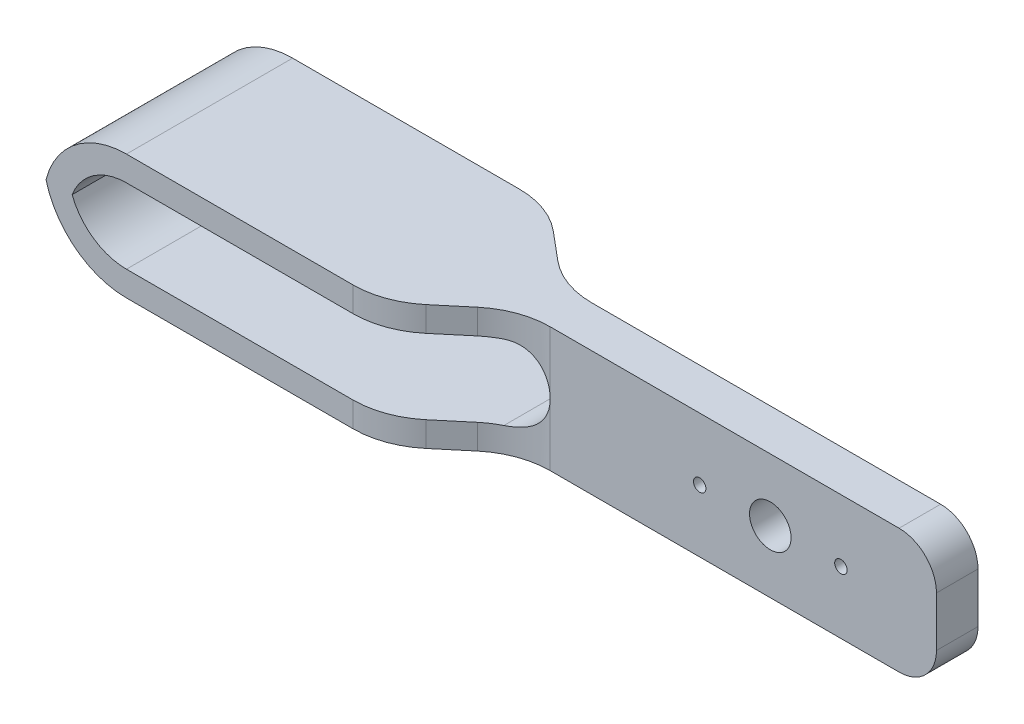
SolidWorks part; units mm, degrees
ref_plane "Plano frontal" through (0, 0, 0) normal (0, 0, 1) x (1, 0, 0)
ref_plane "Plano superior" through (0, 0, 0) normal (0, 1, 0) x (1, 0, 0)
ref_plane "Plano direito" through (0, 0, 0) normal (1, 0, 0) x (0, 0, -1)
sketch "Esboço1" plane through (0, 0, 0) normal (0, 0, 1) x (1, 0, 0)
  line L13 (-17.5, -6) -> (22.5, -6)
  line L14 (-17.5, -6) -> (-17.5, 9)
  line L15 (-17.5, 9) -> (22.5, 9)
  line L16 (22.5, -6) -> (22.5, 9)
  dimension "D3" = 15
  dimension "D4" = 40
extrude "Ressalto-extrusão1" add sketch "Esboço1" against normal blind 3 contours L13 L16 L15 L14 region at (2.5, 1.5, 0)
sketch "Esboço2" plane through (0, 0, 0) normal (0, 0, 1) x (1, 0, 0)
  line L0 (-17.5, 9) -> (22.5, -6) construction
  line L7 (-17.5, -6) -> (22.5, 9) construction
  circle A0 centre (2.5, 1.5) radius 2.5
  circle A4 centre (-6, 1.5) radius 0.75
  point P11 (0, 0)
  dimension "D1" = 1.5
  dimension "D3" = 5
  dimension "D2" = 8.5
sketch "Esboço3" plane through (0, 0, 0) normal (0, 0, 1) x (1, 0, 0)
  line L1 (-17.5, -6) -> (22.5, -6)
  line L2 (-17.5, -6) -> (-17.5, 9)
  line L3 (-17.5, 9) -> (22.5, 9)
  line L4 (22.5, -6) -> (22.5, 9)
extrude "Ressalto-extrusão2" add sketch "Esboço3" along normal blind 2
extrude "Corte-extrusão1" cut sketch "Esboço2" along normal up to surface and the other way up to surface up to face at (2.5, 1.5, 2) other way up to face at (2.5, 1.5, -3)
sketch "Esboço4" plane through (0, 9, 0) normal (0, 1, 0) x (1, 0, 0)
  line L0 (22.5, -2) -> (-17.5, -2) construction
  line L1 (6.2, -34.5) -> (-6.2, -34.5)
  line L2 (6.2, -34.5) -> (6.2, -11.5)
  line L3 (6.2, -11.5) -> (-6.2, -11.5)
  line L4 (-6.2, -34.5) -> (-6.2, -11.5)
  line L5 (-17.5, 3) -> (22.5, 3) construction
  line L6 (17.5, -2) -> (-12.5, -2)
  line L7 (17.5, -2) -> (17.5, -42)
  line L8 (17.5, -42) -> (-12.5, -42)
  line L9 (-12.5, -2) -> (-12.5, -42)
  line L10 (-12.5, -2) -> (17.5, -2)
  line L11 (-12.5, -2) -> (-12.5, 3)
  line L12 (-12.5, 3) -> (17.5, 3)
  line L13 (17.5, -2) -> (17.5, 3)
  circle A0 centre (0, -9.75) radius 1.25
  circle A1 centre (0, -36.25) radius 1.25
  point P6 (0, -34.5)
  point P13 (2.5, -2)
  point P14 (2.5, -42)
  line M5 (-17.5, -2) -> (22.5, -2)
  line M7 (22.5, 3) -> (-17.5, 3)
  dimension "D6" = 7.75
  dimension "D7" = 2.5
  dimension "D8" = 26.5
  dimension "D1" = 9.5
  dimension "D2" = 23
  dimension "D3" = 12.4
  dimension "D4" = 30
  dimension "D5" = 40
extrude "Ressalto-extrusão3" [suppressed] add sketch "Esboço4" against normal blind 3 contours L13 L11 M5 M7 | L9 L8 L7 L1 L4 L3 L2 M5
fillet "Filete2" [suppressed] radius 5
fillet "Filete3" [suppressed] radius 10
sketch "Esboço5" plane through (-17.5, 0, 0) normal (-1, 0, 0) x (0, 0, 1)
  line L0 (-3, 9) -> (2, 9) construction
  line L1 (-10.5, -6) -> (9.5, -6)
  line L2 (-10.5, -6) -> (-10.5, 9)
  line L3 (-10.5, 9) -> (9.5, 9)
  line L4 (9.5, -6) -> (9.5, 9)
  line L5 (-3, -6) -> (2, -6) construction
  point P13 (-0.5, -6)
  point P14 (-0.5, -6)
  dimension "D1" = 20
extrude "Ressalto-extrusão4" add sketch "Esboço5" along normal blind 60
chamfer "Chanfro1" distance 16 angle 50 2 edges at (-17.5, 1.5, 9.5) (-17.5, 1.5, -10.5) first distance on face at (-17.5, 1.5, 5.75) first distance on face at (-17.5, 1.5, -6.75)
fillet "Filete4" radius 10 6 edges at (-36.5681, 1.5, 9.5) (-27.6299, 1.5, 2) (-77.5, 9, -0.5) (-77.5, -6, -0.5) (-36.5681, 1.5, -10.5) (-27.6299, 1.5, -3)
sketch "Esboço6" plane through (0, 0, 9.5) normal (0, 0, 1) x (1, 0, 0)
  line L0 (-43.2078, 6) -> (-67.5, 6)
  line L1 (-67.5, -3) -> (-43.2078, -3)
  line L2 (-43.2078, -3) -> (-43.2078, 6) construction
  line L3 (-40.2078, 9) -> (-67.5, 9)
  line L4 (-67.5, -6) -> (-40.2078, -6)
  line L5 (-40.2078, -6) -> (-40.2078, 9)
  line L6 (-40.2078, 9) -> (-67.5, 9) construction
  line L7 (-67.5, -6) -> (-40.2078, -6) construction
  line L8 (-40.2078, -6) -> (-40.2078, 9) construction
  line L9 (-43.2078, 6) -> (-23.9902, 6)
  line L10 (-23.9902, 9) -> (-23.9902, -6) construction
  line L11 (-43.2078, -3) -> (-23.9902, -3)
  line L12 (-23.9902, -3) -> (-23.9902, 6)
  arc A0 (-67.5, 6) -> (-74.0383, 1.5) centre (-67.5, -1) ccw
  arc A1 (-74.0383, 1.5) -> (-67.5, -3) centre (-67.5, 4) ccw
  arc A2 (-67.5, 9) -> (-77.1825, 1.5) centre (-67.5, -1) ccw
  arc A3 (-77.1825, 1.5) -> (-67.5, -6) centre (-67.5, 4) ccw
  arc A4 (-67.5, 9) -> (-77.1825, 1.5) centre (-67.5, -1) ccw construction
  arc A5 (-77.1825, 1.5) -> (-67.5, -6) centre (-67.5, 4) ccw construction
  dimension "D1" = 0
  dimension "D2" = 3
extrude "Corte-extrusão2" cut sketch "Esboço6" against normal through all
fillet "Filete5" radius 4.5 4 edges at (-23.9902, -3, -0.5) (-23.9902, 6, -0.5) (22.5, -6, -0.5) (22.5, 9, -0.5)
pattern_circular "CirPattern1" count 2 over 360 about axis through (2.5, 1.5, 2) along (0, 0, -1) of "Corte-extrusão1"
